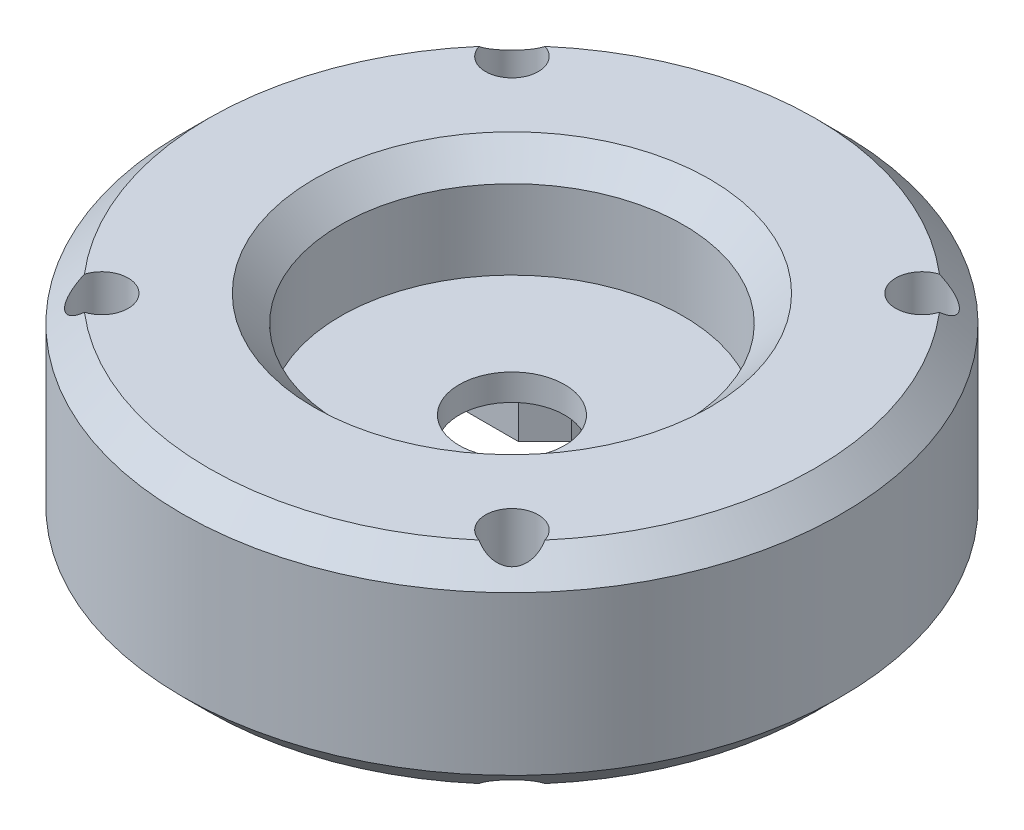
SolidWorks part; units mm, degrees
ref_plane "Front Plane" through (0, 0, 0) normal (0, 0, 1) x (1, 0, 0)
ref_plane "Top Plane" through (0, 0, 0) normal (0, 1, 0) x (1, 0, 0)
ref_plane "Right Plane" through (0, 0, 0) normal (1, 0, 0) x (0, 0, -1)
sketch "Sketch1" plane through (0, 0, 0) normal (0, 1, 0) x (1, 0, 0)
  circle A0 centre (0, 0) radius 12.5
  dimension "D1" = 25
extrude "Boss-Extrude1" add sketch "Sketch1" along normal blind 8
sketch "Sketch2" plane through (0, 8, 0) normal (0, 1, 0) x (1, 0, 0)
  circle A0 centre (0, 0) radius 6.5
  dimension "D1" = 13
extrude "Cut-Extrude1" cut sketch "Sketch2" against normal blind 4
sketch "Sketch4" plane through (0, 0, 0) normal (0, -1, 0) x (-1, 0, 0)
  circle A0 centre (0, 0) radius 2
  dimension "D1" = 4
extrude "Cut-Extrude3" cut sketch "Sketch4" against normal blind 4
sketch "Sketch5" plane through (0, 0, 0) normal (0, -1, 0) x (-1, 0, 0)
  line L13 (10, -3.25) -> (-10, -3.25)
  line L14 (10, -3.25) -> (10, 3.25)
  line L15 (10, 3.25) -> (-10, 3.25)
  line L16 (-10, -3.25) -> (-10, 3.25)
  line L17 (2, -9.25) -> (-2, -9.25)
  line L18 (2, -9.25) -> (2, 9.25)
  line L19 (2, 9.25) -> (-2, 9.25)
  line L20 (-2, -9.25) -> (-2, 9.25)
  point P4 (0, -3.25)
  point P9 (10, 0)
  point P15 (0, -9.25)
  point P17 (-2, 0)
  circle M11 centre (0, 0) radius 2
  dimension "D1" = 0
  dimension "D2" = 0
  dimension "D3" = 20
  dimension "D4" = 0
  dimension "D5" = 0
  dimension "D6" = 4
  dimension "D7" = 6.5
  dimension "D8" = 6
extrude "Cut-Extrude4" cut sketch "Sketch5" against normal blind 3 contours L20 L17 L18 L13 | L13 L20 L15 L16 | L20 L13 L18 M11 | L20 L15 L18 L19 | L18 L13 L14 L15 | L20 L18 L15 M11 region at (-6, 0, 0) region at (0, 0, 6.25) region at (0, 0, 2.3511) region at (6, 0, 0) region at (0, 0, -2.3511) region at (0, 0, -6.25)
sketch "Sketch3" plane through (0, 8, 0) normal (0, 1, 0) x (1, 0, 0)
  circle A1 centre (7.7782, 7.7782) radius 1
  circle A9 centre (0, 0) radius 6.5 construction
  circle A10 centre (7.7782, -7.7782) radius 1
  circle A11 centre (-7.7782, -7.7782) radius 1
  circle A12 centre (-7.7782, 7.7782) radius 1
  dimension "D1" = 11
extrude "Cut-Extrude2" cut sketch "Sketch3" against normal through all
chamfer "Chamfer1" distance 1 angle 45 3 edges at (0, 8, 12.5) (0, 0, 12.5) (0, 8, 6.5)
chamfer "Chamfer2" distance 1 angle 45 4 edges at (-2, 1.5, 3.25) (-2, 1.5, -3.25) (2, 1.5, -3.25) (2, 1.5, 3.25)
